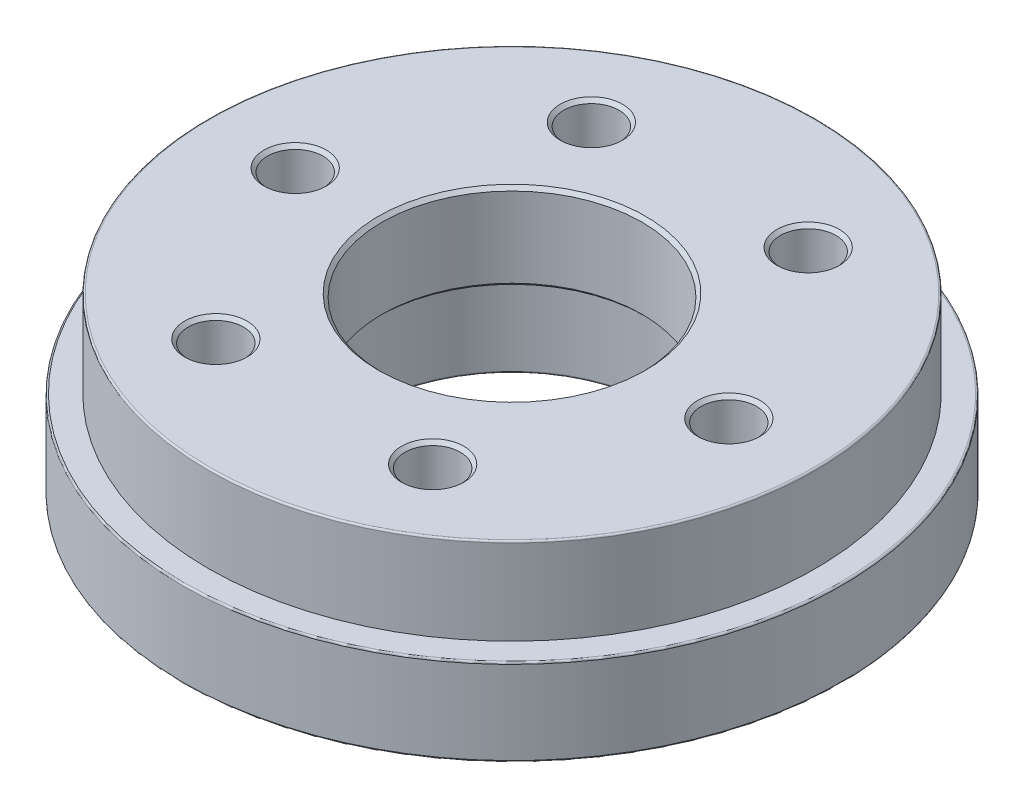
SolidWorks part; units mm, degrees
ref_plane "前视基准面" through (0, 0, 0) normal (0, 0, 1) x (1, 0, 0)
ref_plane "上视基准面" through (0, 0, 0) normal (0, 1, 0) x (1, 0, 0)
ref_plane "右视基准面" through (0, 0, 0) normal (1, 0, 0) x (0, 0, -1)
other "Configuration Table"
sketch "草图1" plane through (0, 0, 0) normal (0, 1, 0) x (1, 0, 0)
  circle A0 centre (0, 0) radius 19
  circle A1 centre (0, 0) radius 15 construction
  circle A2 centre (0, 15) radius 3.1
  circle A3 centre (12.9904, 7.5) radius 3.1
  circle A4 centre (12.9904, -7.5) radius 3.1
  circle A5 centre (0, -15) radius 3.1
  circle A6 centre (-12.9904, -7.5) radius 3.1
  circle A7 centre (-12.9904, 7.5) radius 3.1
  point P18 (0, 0)
  dimension "D1" = 6.2
  dimension "D2" = 38
  dimension "D3" = 30
  dimension "D4" = 6
extrude "凸台-拉伸1" add sketch "草图1" along normal blind 5 contours A0
extrude "切除-拉伸1" cut sketch "草图1<3>" along normal blind 4 contours A7 | A6 | A5 | A4 | A3 | A2 region at (0, 0, -15) region at (12.9904, 0, -7.5) region at (12.9904, 0, 7.5) region at (0, 0, 15) region at (-12.9904, 0, 7.5) region at (-12.9904, 0, -7.5)
sketch "草图1<3>" plane through (0, 0, 0) normal (0, 1, 0) x (1, 0, 0) same geometry as "草图1"
sketch "草图5" plane through (0, 5, 0) normal (0, 1, 0) x (1, 0, 0)
  circle A1 centre (0, 0) radius 17.5
  dimension "D1" = 35
extrude "凸台-拉伸3" add sketch "草图5" along normal blind 5
sketch "草图7" plane through (0, 0, 0) normal (0, -1, 0) x (1, 0, 0)
  circle A0 centre (0, 0) radius 8.5
  dimension "D1" = 17
extrude "切除-拉伸2" cut sketch "草图7" against normal blind 5
sketch "草图8" plane through (0, 5, 0) normal (0, -1, 0) x (1, 0, 0)
  circle A0 centre (0, 0) radius 7.5
  dimension "D1" = 15
extrude "切除-拉伸3" cut sketch "草图8" against normal blind 0.5
sketch "草图10" plane through (0, 0, 0) normal (0, -1, 0) x (1, 0, 0)
  line L0 (0, 15) -> (12.9904, 7.5) construction
  line L2 (6.25, 10.8253) -> (0, 0) construction
  circle A0 centre (0, 0) radius 12.5 construction
  circle A1 centre (6.25, 10.8253) radius 1.6
  circle A2 centre (12.5, 0) radius 1.6
  circle A3 centre (6.25, -10.8253) radius 1.6
  circle A4 centre (-6.25, -10.8253) radius 1.6
  circle A5 centre (-12.5, 0) radius 1.6
  circle A6 centre (-6.25, 10.8253) radius 1.6
  point P21 (0, 0)
  dimension "D1" = 3.2
  dimension "D3" = 25
  dimension "D2" = 6
extrude "切除-拉伸4" cut sketch "草图10" against normal up to next
sketch "草图11" plane through (0, 0, 0) normal (0, -1, 0) x (1, 0, 0)
  line L0 (6.25, -14.0007) -> (9, -12.413)
  line L1 (15.25, -1.5877) -> (15.25, 1.5877)
  line L2 (15.25, 1.5877) -> (12.5, 3.1754)
  line L3 (12.5, 3.1754) -> (9.75, 1.5877)
  line L4 (9.75, 1.5877) -> (9.75, -1.5877)
  line L5 (9.75, -1.5877) -> (12.5, -3.1754)
  line L6 (12.5, -3.1754) -> (15.25, -1.5877)
  line L7 (9, -12.413) -> (9, -9.2376)
  line L8 (9, -9.2376) -> (6.25, -7.6499)
  line L9 (6.25, -7.6499) -> (3.5, -9.2376)
  line L10 (3.5, -9.2376) -> (3.5, -12.413)
  line L11 (3.5, -12.413) -> (6.25, -14.0007)
  line L12 (-9, -12.413) -> (-6.25, -14.0007)
  line L13 (-6.25, -14.0007) -> (-3.5, -12.413)
  line L14 (-3.5, -12.413) -> (-3.5, -9.2376)
  line L15 (-3.5, -9.2376) -> (-6.25, -7.6499)
  line L16 (-6.25, -7.6499) -> (-9, -9.2376)
  line L17 (-9, -9.2376) -> (-9, -12.413)
  line L18 (-15.25, 1.5877) -> (-15.25, -1.5877)
  line L19 (-15.25, -1.5877) -> (-12.5, -3.1754)
  line L20 (-12.5, -3.1754) -> (-9.75, -1.5877)
  line L21 (-9.75, -1.5877) -> (-9.75, 1.5877)
  line L22 (-9.75, 1.5877) -> (-12.5, 3.1754)
  line L23 (-12.5, 3.1754) -> (-15.25, 1.5877)
  line L24 (-6.25, 14.0007) -> (-9, 12.413)
  line L25 (-9, 12.413) -> (-9, 9.2376)
  line L26 (-9, 9.2376) -> (-6.25, 7.6499)
  line L27 (-6.25, 7.6499) -> (-3.5, 9.2376)
  line L28 (-3.5, 9.2376) -> (-3.5, 12.413)
  line L29 (-3.5, 12.413) -> (-6.25, 14.0007)
  line L30 (9, 12.413) -> (6.25, 14.0007)
  line L31 (6.25, 14.0007) -> (3.5, 12.413)
  line L32 (3.5, 12.413) -> (3.5, 9.2376)
  line L33 (3.5, 9.2376) -> (6.25, 7.6499)
  line L34 (6.25, 7.6499) -> (9, 9.2376)
  line L35 (9, 9.2376) -> (9, 12.413)
  circle A0 centre (12.5, 0) radius 2.75 construction
  point P41 (0, 0)
  dimension "D1" = 5.5
  dimension "D2" = 6
extrude "切除-拉伸5" cut sketch "草图11" against normal blind 3
sketch "草图12" plane through (0, 10, 0) normal (0, 1, 0) x (1, 0, 0)
  circle A0 centre (0, 0) radius 7.5
  dimension "D1" = 15
extrude "切除-拉伸6" cut sketch "草图12" against normal up to next
chamfer "倒角1" distance 0.2 angle 45 14 edges at (-12.5, 3, -1.6) (-12.5, 10, 1.6) (-6.25, 3, 9.2253) (-6.25, 10, 12.4253) (6.25, 3, 9.2253) (6.25, 10, 12.4253) (12.5, 3, -1.6) (12.5, 10, 1.6) (6.25, 3, -12.4253) (6.25, 10, -9.2253) (-6.25, 3, -12.4253) (-6.25, 10, -9.2253) (0, 10, 7.5) (0, 5, -7.5)
fillet "圆角1" radius 0.1 4 edges at (0, 0, 19) (0, 5, 19) (0, 0, -8.5) (0, 10, 17.5)
fillet "圆角2" radius 0.1 6 edges at (12.9904, 0, 10.6) (12.9904, 0, -4.4) (0, 0, -11.9) (-12.9904, 0, -4.4) (-12.9904, 0, 10.6) (0, 0, 18.1)
